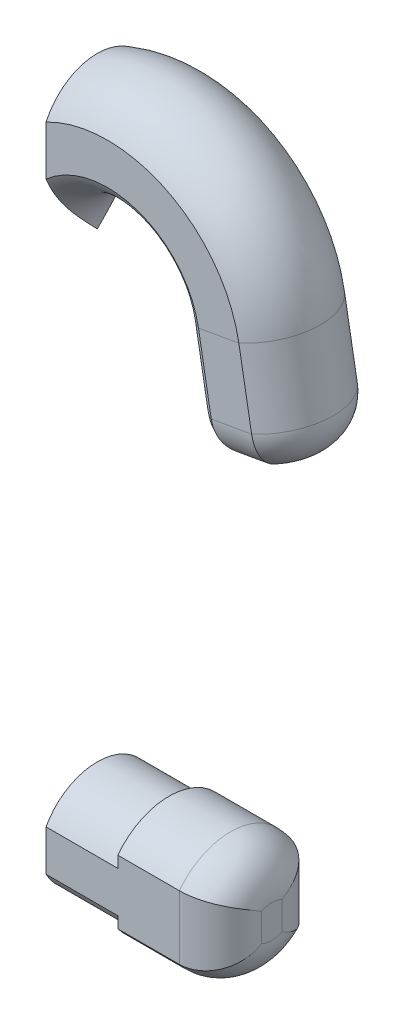
SolidWorks part; units mm, degrees
ref_plane "前视基准面" through (0, 0, 0) normal (0, 0, 1) x (1, 0, 0)
ref_plane "上视基准面" through (0, 0, 0) normal (0, 1, 0) x (1, 0, 0)
ref_plane "右视基准面" through (0, 0, 0) normal (1, 0, 0) x (0, 0, -1)
other "Configuration Table"
sketch "草图1" plane through (0, 0, 0) normal (0, 0, 1) x (1, 0, 0)
  line L0 (0, 0) -> (0, 25)
  line L1 (10.9164, 25.9551) -> (11.8862, 20.4551)
  line L2 (0, 0) -> (0, -3)
  arc A0 (0, 25) -> (10.9164, 25.9551) centre (5.5, 25) cw
  dimension "D1" = 5.5
  dimension "D2" = 10
  dimension "D3" = 25
  dimension "6" = 5.5
ref_plane "基准面3" through (0, -3, 0) normal (0, 1, 0) x (1, 0, 0)
sketch "草图13" plane through (0, -3, 0) normal (0, 1, 0) x (1, 0, 0)
  line L1 (-1, -2.5) -> (1, -2.5)
  line L3 (-1, 2.5) -> (1, 2.5)
  line L5 (-1, -2.5) -> (1, 2.5) construction
  line L6 (-1, 2.5) -> (1, -2.5) construction
  line L7 (0, 2.5) -> (0, -2.5) construction
  line L8 (1, 2.5) -> (1, -2.5) construction
  arc A0 (1, 2.5) -> (1, -2.5) centre (-0.3333, 0) cw
  arc A1 (-1, 2.5) -> (-1, -2.5) centre (0.3333, 0) ccw
  point P11 (1, 0)
  point P12 (2.5, 0)
  point P21 (0, 0)
  dimension "D2" = 2
  dimension "D1" = 5
  dimension "D3" = 1.5
sweep "扫描2" add profiles "草图13" path "草图1"
sketch "草图15" plane through (0, 0, 0) normal (0, 0, 1) x (1, 0, 0)
  line L0 (10.9164, 25.9551) -> (11.8862, 20.4551) construction
  line L1 (0, 0) -> (0, 25) construction
  line L3 (10.9164, 25.9551) -> (11.8862, 20.4551) construction
  line L4 (0, 0) -> (0, 25) construction
  line L5 (0, 0) -> (11, 0)
  arc A0 (10.9164, 25.9551) -> (0, 25) centre (5.5, 25) ccw construction
  arc A2 (10.9164, 25.9551) -> (0, 25) centre (5.5, 25) ccw construction
  dimension "D1" = 11
ref_plane "基准面2" through (11, 0, 0) normal (1, 0, 0) x (0, 0, -1)
sketch "草图16" plane through (11, 0, 0) normal (1, 0, 0) x (0, 0, -1)
  line L2 (-2.5, 0) -> (2.5, 0) construction
  line L4 (-2.5, -1) -> (-2.5, 1)
  line L6 (2.5, -1) -> (2.5, 1)
  line L7 (-2.5, -1) -> (2.5, 1) construction
  line L8 (-2.5, 1) -> (2.5, -1) construction
  line L9 (-2.5, -1) -> (2.5, -1) construction
  arc A3 (-2.5, -1) -> (2.5, -1) centre (0, 0.3333) ccw
  arc A4 (-2.5, 1) -> (2.5, 1) centre (0, -0.3333) cw
  point P0 (0, 0)
  point P9 (0, -2.5)
  dimension "D1" = 2
  dimension "D2" = 1.5
  dimension "D3" = 5
sweep "扫描4" add profiles "草图16" path "草图15"
sketch "草图17" plane through (11, 0, 0) normal (1, 0, 0) x (0, 0, -1)
  line L0 (-2.5, 1) -> (-2.5, -1) construction
  line L1 (-2.5, 1.5555) -> (-2.5, -1.5555)
  line L2 (2.5, -1) -> (2.5, 1) construction
  line L3 (2.5, -1) -> (2.5, 1) construction
  line L6 (2.5, 1.5555) -> (2.5, -1.5555)
  line L7 (2.5, 25) -> (2.5, 0) construction
  line L10 (-2.8, 1.073) -> (-2.8, -1.073)
  line L11 (2.8, -1.073) -> (2.8, 1.073)
  line L12 (-2.5, 0) -> (2.5, 0) construction
  arc A0 (2.5, -1.5555) -> (-2.5, -1.5555) centre (0, 0.3333) cw
  arc A15 (2.8, 1.073) -> (-2.8, 1.073) centre (0, -0.3333) ccw
  arc A16 (-2.8, -1.073) -> (2.8, -1.073) centre (0, 0.3333) ccw
  arc A17 (2.5, 1.5555) -> (-2.5, 1.5555) centre (0, -0.3333) ccw
  dimension "D1" = 0.3
extrude "凸台-拉伸1" add sketch "草图17" against normal blind 5
ref_plane "基准面4" through (1, 0, 0) normal (1, 0, 0) x (0, 0, -1)
sketch "草图19" plane through (1, 0, 0) normal (1, 0, 0) x (0, 0, -1)
  line L1 (-2.5, 5) -> (2.5, 5)
  line L2 (2.5, 0) -> (2.5, 25)
  line L3 (-2.5, 25) -> (-2.5, 0)
  line L4 (2.5, 5) -> (2.5, 23)
  line L5 (-2.5, 23) -> (-2.5, 5)
  line L6 (-2.5, 23) -> (2.5, 23)
  line L7 (0, 0) -> (0, 23) construction
  line L11 (2.5, 25) -> (-2.5, 25)
  line L12 (-2.5, 0) -> (2.5, 0)
  dimension "D2" = 18
  dimension "D3" = 5
  dimension "D1" = 0
extrude "凸台-拉伸2" add sketch "草图19" along normal blind 1.5
fillet "圆角2" radius 2 8 edges at (11.8862, 20.4551, 2.5) (14.3483, 20.8892, 0) (11.8862, 20.4551, -2.5) (9.4242, 20.0209, 0) (11, -2.8, 0) (11, 0, 2.5) (11, 2.8, 0) (11, 0, -2.5)
sketch "草图20" plane through (2.5, 0, 0) normal (1, 0, 0) x (0, 0, -1)
  line L0 (-2.5, 14) -> (2.5, 14) construction
  line L1 (-6.5, -6) -> (6.5, -6)
  line L2 (-6.5, -6) -> (-6.5, 34)
  line L3 (-6.5, 34) -> (6.5, 34)
  line L4 (6.5, -6) -> (6.5, 34)
  line L5 (-6.5, -6) -> (6.5, 34) construction
  line L6 (-6.5, 34) -> (6.5, -6) construction
  line L7 (-2.5, 23) -> (-2.5, 5) construction
  line L8 (2.5, 5) -> (2.5, 23) construction
  point P0 (0, 14)
  dimension "D1" = 40
  dimension "D2" = 13
extrude "切除-拉伸1" cut sketch "草图20" against normal blind 10
